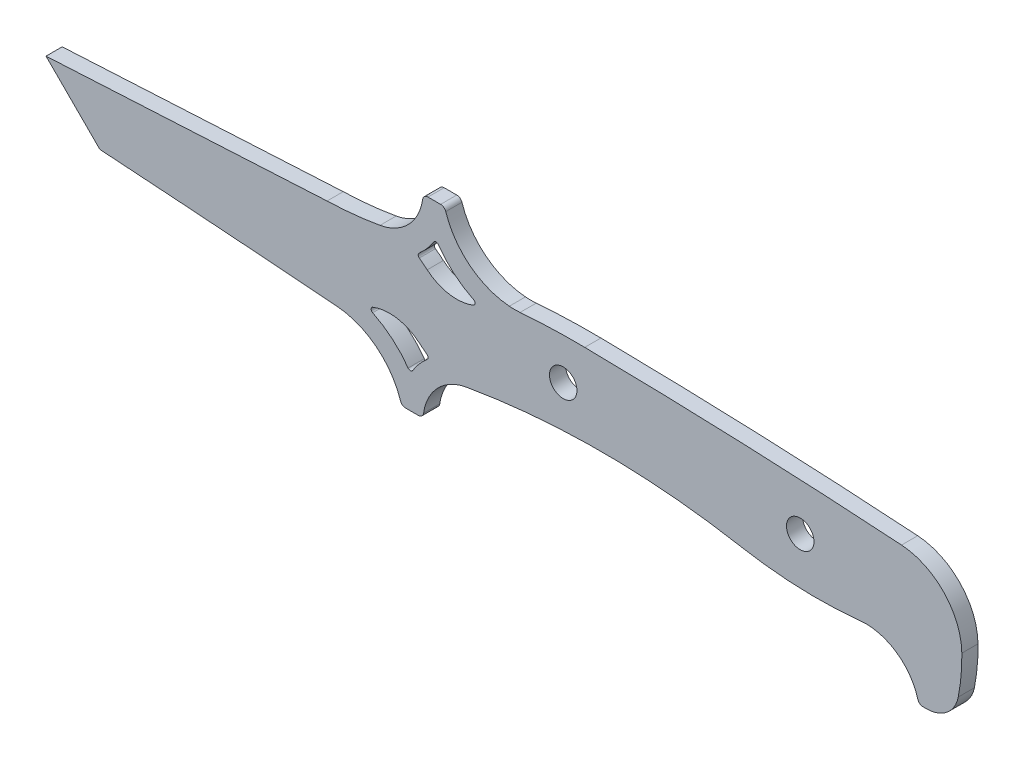
SolidWorks part; units mm, degrees
ref_plane "前视基准面" through (0, 0, 0) normal (0, 0, 1) x (1, 0, 0)
ref_plane "上视基准面" through (0, 0, 0) normal (0, 1, 0) x (1, 0, 0)
ref_plane "右视基准面" through (0, 0, 0) normal (1, 0, 0) x (0, 0, -1)
sketch "草图1" plane through (0, 0, 0) normal (0, 0, 1) x (1, 0, 0)
  line L0 (-25.5902, 0) -> (-5.9672, 0) construction
  line L1 (0, 18.5328) -> (0, -16.9262) construction
  line L2 (-70, 0) -> (-60, -10)
  line L3 (-4, -23.2) -> (0, -23.2)
  line L4 (4, 12.8) -> (0, 12.8)
  line L5 (100, 5.844) -> (100, -12.1448) construction
  line L6 (92, -23.2) -> (98, -23.2)
  line L7 (-60.9946, -3.3486) -> (-58.2334, -6.1097)
  arc A0 (-70, 0) -> (-17.8296, 2.8) centre (15, -1096.3179) cw
  arc A1 (-60, -10) -> (-16, -13.2) centre (-320.4503, -3895.2914) cw
  arc A2 (-16, -13.2) -> (-4, -23.2) centre (-17.0562, -26.6674) cw
  arc A3 (-17.8296, 2.8) -> (0, -5.2) centre (-17.1611, -19.5786) cw
  arc A4 (18, -12.8087) -> (0, -5.2) centre (16.843, 9.5499) cw
  arc A5 (0, -23.2) -> (8, -14.2) centre (9.6655, -23.736) cw
  arc A6 (8, -14.2) -> (58.8972, -14.3397) centre (33.055, -157.6545) cw
  arc A7 (16, 2.8) -> (4, 12.8) centre (17.0562, 16.2674) cw
  arc A8 (0, 12.8) -> (-8, 3.8) centre (-9.6655, 13.336) cw
  arc A9 (99.9957, -10.9746) -> (98, -23.2) centre (64.9142, -11.5234) cw
  arc A11 (16, 2.8) -> (18, 2.8) centre (17, 15.5512) ccw
  arc A12 (18, 2.8) -> (30, 3.1879) centre (28.2173, -127.4827) cw
  arc A14 (-17.8296, 2.8) -> (0, 3.1879) centre (15, -1096.3179) cw construction
  arc A15 (30, 3.1879) -> (88.8026, 0.8107) centre (15, -1096.3179) cw
  arc A16 (0, 3.1879) -> (13.3626, 3.289) centre (15, -1096.3179) cw construction
  arc A17 (13.3626, 3.289) -> (30, 3.1879) centre (15, -1096.3179) cw construction
  arc A18 (98, 0.1532) -> (100, 0) centre (15, -1096.3179) cw construction
  arc A19 (81.1808, -15.1996) -> (92, -23.2) centre (82.1916, -25.1484) cw
  arc A20 (-17.8296, 2.8) -> (-8, 3.8) centre (-19.8934, 71.8968) ccw
  arc A21 (99.9957, -10.9746) -> (88.8026, 0.8107) centre (87.9972, -11.1623) ccw
  arc A22 (81.1808, -15.1996) -> (58.8972, -14.3397) centre (73.0937, 64.3906) cw
  arc A23 (-10.3412, -10.4975) -> (-2.3412, -17.1792) centre (-17.0562, -26.6674) cw
  arc A24 (-2.3412, -17.1792) -> (1.239, -12.9589) centre (9.6655, -23.736) cw
  arc A25 (-10.3412, -10.4975) -> (-0.761, -11.4318) centre (-6.2326, -17.9532) cw
  arc A26 (-0.761, -11.4318) -> (1.239, -12.9589) centre (16.843, 9.5499) ccw
  arc A27 (0.761, 1.0318) -> (-1.239, 2.5589) centre (-16.843, -19.9499) ccw
  arc A28 (2.3412, 6.7792) -> (-1.239, 2.5589) centre (-9.6655, 13.336) cw
  arc A29 (10.3412, 0.0975) -> (2.3412, 6.7792) centre (17.0562, 16.2674) cw
  arc A30 (10.3412, 0.0975) -> (0.761, 1.0318) centre (6.2326, 7.5532) cw
  arc A31 (-60.9946, -3.3486) -> (-59, -3.2117) centre (15, -1096.3179) cw
  arc A32 (-59, -3.2117) -> (-44, 1.7062) centre (-61.1613, 28.7148) ccw
  arc A33 (-58.2334, -6.1097) -> (-26, -8.4172) centre (-320.4503, -3895.2914) cw
  arc A34 (-26, -8.4172) -> (-7.1888, -17.4412) centre (-28.1697, -37.0588) cw
  circle A35 centre (70, -6.8) radius 2.55
  circle A36 centre (26, -4.5) radius 2.55
  point P16 (-17.8296, 2.8)
  point P58 (75, -18.2)
  dimension "D1" = 70
  dimension "D5" = 2.8
  dimension "D6" = 2
  dimension "D8" = 8
  dimension "D12" = 6
  dimension "D18" = 10
  dimension "D24" = 12
  dimension "D25" = 80
  dimension "D26" = 4
  dimension "D27" = 4
  dimension "D28" = 5
  dimension "D29" = 2
  dimension "D32" = 4
  dimension "D34" = 4
  dimension "D37" = 26
  dimension "D38" = 5.1
  dimension "D39" = 5.1
  dimension "D2" = 100
  dimension "D3" = 45
  dimension "D4" = 10
  dimension "D9" = 4
  dimension "D10" = 16
  dimension "D11" = 10
  dimension "D13" = 30
  dimension "D14" = 18
  dimension "D15" = 10
  dimension "D16" = 25
  dimension "D17" = 5
  dimension "D19" = 2.8
  dimension "D20" = 36
  dimension "D21" = 18
  dimension "D22" = 9
  dimension "D23" = 2
  dimension "D30" = 8
  dimension "D33" = 4
  dimension "D35" = 26
  dimension "D36" = 15
  dimension "D40" = 6.8
  dimension "D41" = 30
  dimension "D42" = 26
  dimension "D43" = 4.5
  dimension "D7" = 2
  dimension "D31" = 2
sketch "草图2" plane through (0, 0, 2) normal (0, 0, 1) x (1, 0, 0)
  line L0 (-60.9946, -3.3486) -> (-58.2334, -6.1097) construction
  line L2 (-4, -23.2) -> (0, -23.2) construction
  line L3 (92, -23.2) -> (98, -23.2) construction
  line L4 (4, 12.8) -> (0, 12.8) construction
  line L5 (-60.9946, -3.3486) -> (-58.2334, -6.1097)
  line L7 (-4, -23.2) -> (0, -23.2)
  line L8 (92, -23.2) -> (98, -23.2)
  line L9 (4, 12.8) -> (0, 12.8)
  arc A2 (-7.1888, -17.4412) -> (-26, -8.4172) centre (-28.1697, -37.0588) ccw construction
  arc A3 (-26, -8.4172) -> (-58.2334, -6.1097) centre (-320.4503, -3895.2914) ccw construction
  arc A4 (-59, -3.2117) -> (-60.9946, -3.3486) centre (15, -1096.3179) ccw construction
  arc A5 (-59, -3.2117) -> (-44, 1.7062) centre (-61.1613, 28.7148) ccw construction
  arc A6 (-17.8296, 2.8) -> (-70, 0) centre (15, -1096.3179) ccw construction
  arc A8 (-4, -23.2) -> (-16, -13.2) centre (-17.0562, -26.6674) ccw construction
  arc A9 (8, -14.2) -> (0, -23.2) centre (9.6655, -23.736) ccw construction
  arc A10 (58.8972, -14.3397) -> (8, -14.2) centre (33.055, -157.6545) ccw construction
  arc A11 (58.8972, -14.3397) -> (81.1808, -15.1996) centre (73.0937, 64.3906) ccw construction
  arc A12 (92, -23.2) -> (81.1808, -15.1996) centre (82.1916, -25.1484) ccw construction
  arc A13 (98, -23.2) -> (99.9957, -10.9746) centre (64.9142, -11.5234) ccw construction
  arc A14 (99.9957, -10.9746) -> (88.8026, 0.8107) centre (87.9972, -11.1623) ccw construction
  arc A15 (88.8026, 0.8107) -> (30, 3.1879) centre (15, -1096.3179) ccw construction
  arc A16 (30, 3.1879) -> (18, 2.8) centre (28.2173, -127.4827) ccw construction
  arc A17 (16, 2.8) -> (18, 2.8) centre (17, 15.5512) ccw construction
  arc A18 (4, 12.8) -> (16, 2.8) centre (17.0562, 16.2674) ccw construction
  arc A19 (-8, 3.8) -> (0, 12.8) centre (-9.6655, 13.336) ccw construction
  arc A20 (-17.8296, 2.8) -> (-8, 3.8) centre (-19.8934, 71.8968) ccw construction
  arc A31 (-7.1888, -17.4412) -> (-26, -8.4172) centre (-28.1697, -37.0588) ccw
  arc A32 (-26, -8.4172) -> (-58.2334, -6.1097) centre (-320.4503, -3895.2914) ccw
  arc A33 (-59, -3.2117) -> (-60.9946, -3.3486) centre (15, -1096.3179) ccw
  arc A34 (-59, -3.2117) -> (-44, 1.7062) centre (-61.1613, 28.7148) ccw
  arc A35 (-17.8296, 2.8) -> (-44, 1.7062) centre (15, -1096.3179) ccw
  arc A37 (-4, -23.2) -> (-7.1888, -17.4412) centre (-17.0562, -26.6674) ccw
  arc A38 (8, -14.2) -> (0, -23.2) centre (9.6655, -23.736) ccw
  arc A39 (58.8972, -14.3397) -> (8, -14.2) centre (33.055, -157.6545) ccw
  arc A40 (58.8972, -14.3397) -> (81.1808, -15.1996) centre (73.0937, 64.3906) ccw
  arc A41 (92, -23.2) -> (81.1808, -15.1996) centre (82.1916, -25.1484) ccw
  arc A42 (98, -23.2) -> (99.9957, -10.9746) centre (64.9142, -11.5234) ccw
  arc A43 (99.9957, -10.9746) -> (88.8026, 0.8107) centre (87.9972, -11.1623) ccw
  arc A44 (88.8026, 0.8107) -> (30, 3.1879) centre (15, -1096.3179) ccw
  arc A45 (30, 3.1879) -> (18, 2.8) centre (28.2173, -127.4827) ccw
  arc A46 (16, 2.8) -> (18, 2.8) centre (17, 15.5512) ccw
  arc A47 (4, 12.8) -> (16, 2.8) centre (17.0562, 16.2674) ccw
  arc A48 (-8, 3.8) -> (0, 12.8) centre (-9.6655, 13.336) ccw
  arc A49 (-17.8296, 2.8) -> (-8, 3.8) centre (-19.8934, 71.8968) ccw
sketch "草图3" plane through (0, 0, 0) normal (0, 0, 1) x (1, 0, 0)
  line L0 (-69, 0.0537) -> (-17.8296, 2.8)
  line L1 (-70, 0) -> (-60, -10) construction
  line L2 (-4, -23.2) -> (0, -23.2) construction
  line L3 (92, -23.2) -> (98, -23.2) construction
  line L4 (4, 12.8) -> (0, 12.8) construction
  line L5 (-69, 0.0537) -> (-70, 0)
  line L6 (-70, 0) -> (-60, -10)
  line L7 (-4, -23.2) -> (0, -23.2)
  line L8 (92, -23.2) -> (98, -23.2)
  line L9 (4, 12.8) -> (0, 12.8)
  arc A7 (-16, -13.2) -> (-60, -10) centre (-320.4503, -3895.2914) ccw construction
  arc A8 (-4, -23.2) -> (-16, -13.2) centre (-17.0562, -26.6674) ccw construction
  arc A9 (8, -14.2) -> (0, -23.2) centre (9.6655, -23.736) ccw construction
  arc A10 (58.8972, -14.3397) -> (8, -14.2) centre (33.055, -157.6545) ccw construction
  arc A11 (58.8972, -14.3397) -> (81.1808, -15.1996) centre (73.0937, 64.3906) ccw construction
  arc A12 (92, -23.2) -> (81.1808, -15.1996) centre (82.1916, -25.1484) ccw construction
  arc A13 (98, -23.2) -> (99.9957, -10.9746) centre (64.9142, -11.5234) ccw construction
  arc A14 (99.9957, -10.9746) -> (88.8026, 0.8107) centre (87.9972, -11.1623) ccw construction
  arc A15 (88.8026, 0.8107) -> (30, 3.1879) centre (15, -1096.3179) ccw construction
  arc A16 (30, 3.1879) -> (18, 2.8) centre (28.2173, -127.4827) ccw construction
  arc A17 (16, 2.8) -> (18, 2.8) centre (17, 15.5512) ccw construction
  arc A18 (4, 12.8) -> (16, 2.8) centre (17.0562, 16.2674) ccw construction
  arc A19 (-8, 3.8) -> (0, 12.8) centre (-9.6655, 13.336) ccw construction
  arc A20 (-17.8296, 2.8) -> (-8, 3.8) centre (-19.8934, 71.8968) ccw construction
  arc A36 (-16, -13.2) -> (-60, -10) centre (-320.4503, -3895.2914) ccw
  arc A37 (-4, -23.2) -> (-16, -13.2) centre (-17.0562, -26.6674) ccw
  arc A38 (8, -14.2) -> (0, -23.2) centre (9.6655, -23.736) ccw
  arc A39 (58.8972, -14.3397) -> (8, -14.2) centre (33.055, -157.6545) ccw
  arc A40 (58.8972, -14.3397) -> (81.1808, -15.1996) centre (73.0937, 64.3906) ccw
  arc A41 (92, -23.2) -> (81.1808, -15.1996) centre (82.1916, -25.1484) ccw
  arc A42 (98, -23.2) -> (99.9957, -10.9746) centre (64.9142, -11.5234) ccw
  arc A43 (99.9957, -10.9746) -> (88.8026, 0.8107) centre (87.9972, -11.1623) ccw
  arc A44 (88.8026, 0.8107) -> (30, 3.1879) centre (15, -1096.3179) ccw
  arc A45 (30, 3.1879) -> (18, 2.8) centre (28.2173, -127.4827) ccw
  arc A46 (16, 2.8) -> (18, 2.8) centre (17, 15.5512) ccw
  arc A47 (4, 12.8) -> (16, 2.8) centre (17.0562, 16.2674) ccw
  arc A48 (-8, 3.8) -> (0, 12.8) centre (-9.6655, 13.336) ccw
  arc A49 (-17.8296, 2.8) -> (-8, 3.8) centre (-19.8934, 71.8968) ccw
  point P0 (-69, 0.0537)
  dimension "D1" = 1
extrude "凸台-拉伸1" add sketch "草图3" along normal mid plane 3
extrude "切除-拉伸1" cut sketch "草图1" against normal through all both and the other way through all contours A30 A29 A28 A27 | A26 A25 A23 A24 region at (-3.9097, -12.373, 0) region at (3.9097, 1.973, 0)
fillet "圆角2" radius 0.5 6 edges at (-10.3412, -10.4975, 0) (-2.3412, -17.1792, 0) (1.239, -12.9589, 0) (10.3412, 0.0975, 0) (2.3412, 6.7792, 0) (-1.239, 2.5589, 0)
extrude "切除-拉伸2" cut sketch "草图1<3>" against normal through all both and the other way through all contours A36 | A35
sketch "草图1<3>" plane through (0, 0, 0) normal (0, 0, 1) x (1, 0, 0) same geometry as "草图1"
fillet "圆角3" radius 1 5 edges at (0, -23.2, 0) (-4, -23.2, 0) (4, 12.8, 0) (0, 12.8, 0) (92, -23.2, 0)
fillet "圆角4" radius 6 1 edges at (98, -23.2, 0)
